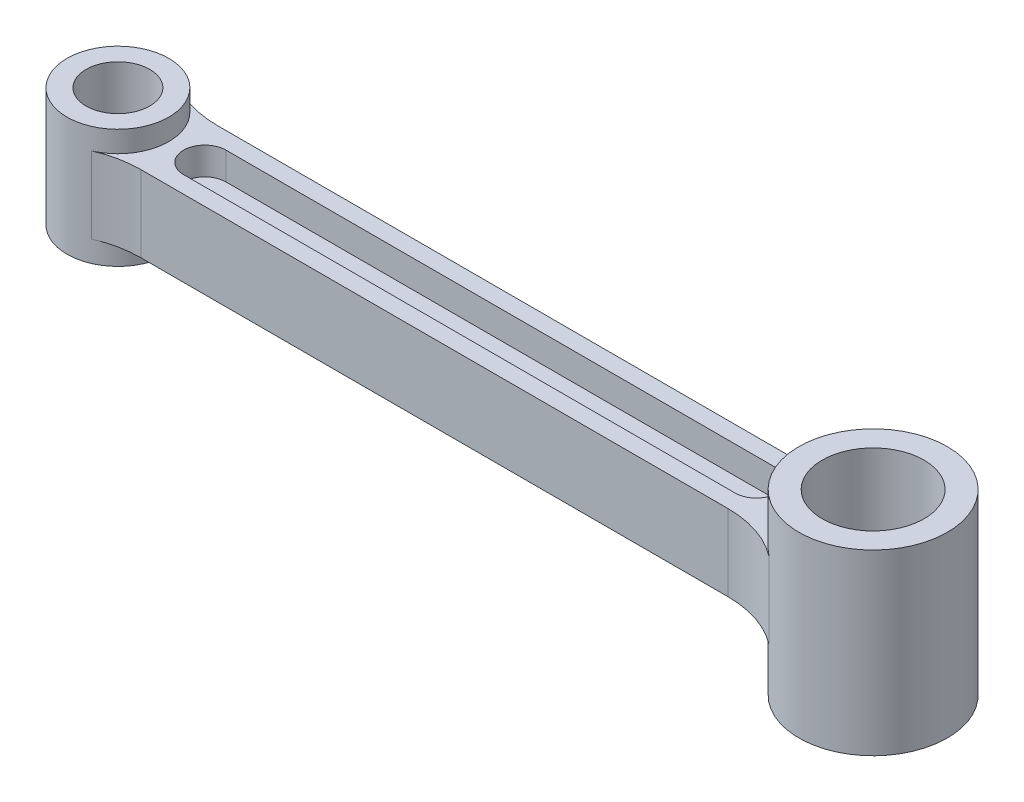
SolidWorks part; units mm, degrees
ref_plane "Front Plane" through (0, 0, 0) normal (0, 0, 1) x (1, 0, 0)
ref_plane "Top Plane" through (0, 0, 0) normal (0, 1, 0) x (1, 0, 0)
ref_plane "Right Plane" through (0, 0, 0) normal (1, 0, 0) x (0, 0, -1)
sketch "Sketch2" plane through (0, 0, 0) normal (0, 0, 1) x (1, 0, 0)
  line L0 (0, 0) -> (0, 18)
  line L1 (0, 18) -> (178, 18)
  line L2 (178, 18) -> (178, 0)
  line L3 (178, 0) -> (0, 0)
  dimension "D1" = 18
  dimension "D2" = 178
extrude "Boss-Extrude1" add sketch "Sketch2" along normal mid plane 18
sketch "Sketch11" plane through (0, 0, 0) normal (0, 0, 1) x (1, 0, 0)
  line L0 (0, -5) -> (0, 23)
  line L1 (5.4421, 9) -> (-13.1931, 9) construction
  line L2 (178, 18) -> (0, 18) construction
  line L3 (0, 0) -> (178, 0) construction
  point P9 (0, 0)
  dimension "D1" = 28
sweep "Sweep2" add path "Sketch11" circular profile diameter 24 parameters "D3"=24
sketch "Sketch18" plane through (0, 0, 0) normal (0, 0, 1) x (1, 0, 0)
  line L0 (178.0093, 30) -> (178.0093, -12)
  line L1 (172.3589, 9) -> (193.9282, 9) construction
  line L2 (178, 18) -> (7.9373, 18) construction
  line L3 (7.9373, 0) -> (178, 0) construction
  point P8 (0, 0)
  point P9 (0, 0)
  point P10 (0, 0)
  dimension "D1" = 42
  dimension "D2" = 178.0093
sweep "Sweep3" add path "Sketch18" circular profile diameter 35 parameters "D3"=35
sketch "Sketch25" plane through (0, 18, 0) normal (0, 1, 0) x (1, 0, 0)
  line L0 (85.4691, -9) -> (85.4691, -19.55) construction
  line L1 (20.4691, 5) -> (150.4691, 5)
  line L3 (20.4691, -5) -> (150.4691, -5)
  line L5 (163.0009, -9) -> (7.9373, -9) construction
  arc A0 (20.4691, 5) -> (20.4691, -5) centre (20.4691, 0) ccw
  arc A1 (150.4691, -5) -> (150.4691, 5) centre (150.4691, 0) ccw
  point P4 (0, 0)
  point P5 (0, 0)
  dimension "D2" = 10
  dimension "D1" = 130
  dimension "D3" = 4
extrude "Cut-Extrude1" cut sketch "Sketch25" against normal blind 6.5
ref_plane "Plane1" through (0, 9, 0) normal (0, 1, 0) x (1, 0, 0)
mirror "Mirror1" about plane through (0, 9, 0) normal (0, 1, 0) of "Cut-Extrude1"
sweep "Cut-Sweep1" cut path "Sketch11<2>" circular profile diameter 15 parameters "D3"=15
sketch "Sketch11<2>" plane through (0, 0, 0) normal (0, 0, 1) x (1, 0, 0) same geometry as "Sketch11"
sweep "Cut-Sweep2" cut path "Sketch18<2>" circular profile diameter 24 parameters "D3"=24
sketch "Sketch18<2>" plane through (0, 0, 0) normal (0, 0, 1) x (1, 0, 0) same geometry as "Sketch18"
fillet "Fillet1" radius 24 4 edges at (163.0009, 9, 9) (163.0009, 9, -9) (7.9373, 9, -9) (7.9373, 9, 9)
